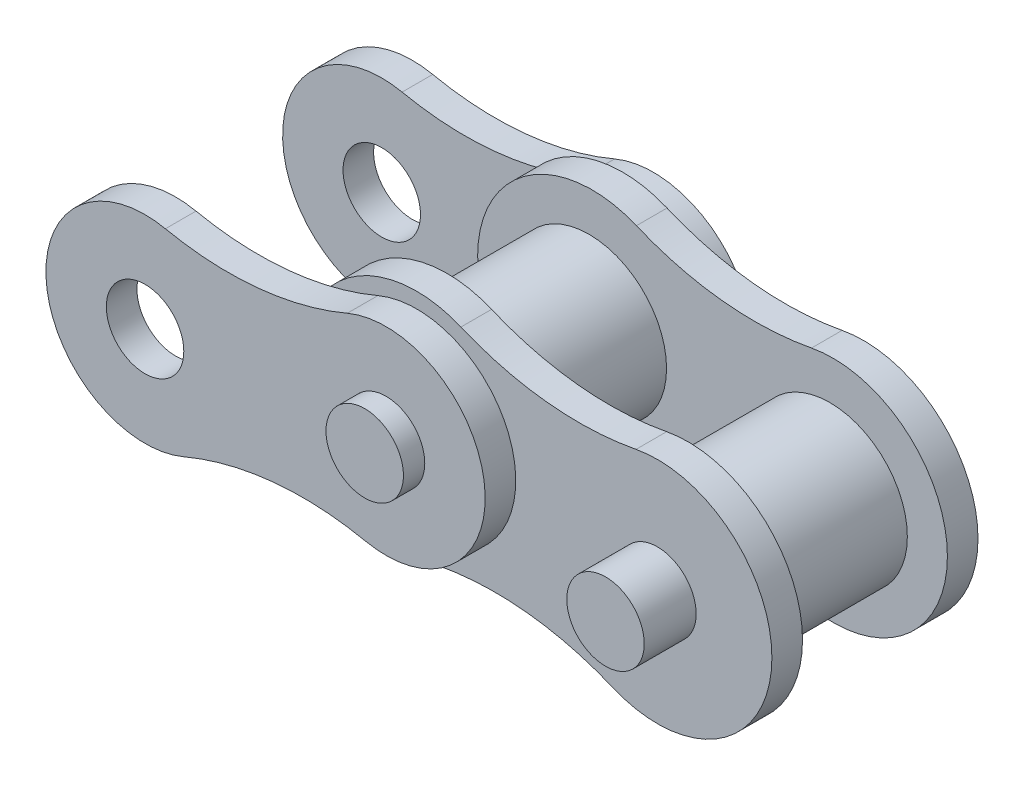
SolidWorks part; units mm, degrees
ref_plane "Front Plane" through (0, 0, 0) normal (0, 0, 1) x (1, 0, 0)
ref_plane "Top Plane" through (0, 0, 0) normal (0, 1, 0) x (1, 0, 0)
ref_plane "Right Plane" through (0, 0, 0) normal (1, 0, 0) x (0, 0, -1)
sketch "Sketch5" plane through (0, 0, 0) normal (0, 0, 1) x (1, 0, 0)
  line L0 (-11.651, 75.0374) -> (-172.0056, 50.1392) construction
  line L1 (-172.0056, -50.1392) -> (-11.651, -75.0374) construction
  arc A0 (-172.0056, 50.1392) -> (-172.0056, -50.1392) centre (-164.2205, 0) ccw construction
  arc A1 (-11.651, -75.0374) -> (-11.651, 75.0374) centre (0, 0) ccw construction
  spline S0 degree 3 poles (-11.5673, -75.0503) (37.9253, -82.6785) (75.9365, -50.077) (75.9365, 0) (75.9365, 50.077) (37.9253, 82.6785) (-11.5673, 75.0503) (-11.5766, 75.0489) (-11.5952, 75.046) (-11.6231, 75.0417) (-11.6417, 75.0388) (-11.651, 75.0374) (-11.66, 75.036) (-11.678, 75.0332) (-11.7051, 75.029) (-11.7231, 75.0262) (-11.7321, 75.0248) (-65.1307, 66.7336) (-118.5294, 58.4424) (-171.928, 50.1513) (-171.9366, 50.1499) (-171.9539, 50.1472) (-171.9797, 50.1432) (-171.997, 50.1405) (-172.0056, 50.1392) (-172.0132, 50.138) (-172.0285, 50.1356) (-172.0514, 50.1321) (-172.0667, 50.1297) (-172.0744, 50.1285) (-247.7088, 38.2785) (-247.7088, -38.2785) (-172.0744, -50.1285) (-172.0667, -50.1297) (-172.0514, -50.1321) (-172.0285, -50.1356) (-172.0132, -50.138) (-172.0056, -50.1392) (-171.997, -50.1405) (-171.9797, -50.1432) (-171.9539, -50.1472) (-171.9366, -50.1499) (-171.928, -50.1513) (-118.5294, -58.4424) (-65.1307, -66.7336) (-11.7321, -75.0248) (-11.7231, -75.0262) (-11.7051, -75.029) (-11.678, -75.0332) (-11.66, -75.036) (-11.651, -75.0374) (-11.6417, -75.0388) (-11.6231, -75.0417) (-11.5952, -75.046) (-11.5766, -75.0489) (-11.5673, -75.0503) (37.9253, -82.6785) (75.9365, -50.077) knots -0.000043 0 0 0 0.175818 0.175818 0.175818 0.351636 0.351636 0.351636 0.351679 0.351722 0.351765 0.351765 0.351765 0.351807 0.351849 0.35189 0.35189 0.35189 0.599139 0.599139 0.599139 0.599179 0.599219 0.599259 0.599259 0.599259 0.599294 0.59933 0.599365 0.599365 0.599365 0.752271 0.752271 0.752271 0.752306 0.752342 0.752377 0.752377 0.752377 0.752417 0.752457 0.752497 0.752497 0.752497 0.999746 0.999746 0.999746 0.999787 0.999829 0.999871 0.999871 0.999871 0.999914 0.999957 1 1 1 1.175818 1.175818 1.175818 weights 1 0.767351 0.767351 1 0.767351 0.767351 1 1 1 1 1 1 1 1 1 1 1 1 1 1 1 1 1 1 1 1 1 1 1 1 0.436524 0.436524 1 1 1 1 1 1 1 1 1 1 1 1 1 1 1 1 1 1 1 1 1 1 1 1 0.767351 0.767351 only from (-11.5673, -75.0503) to (-11.5673, -75.0503)
  dimension "D2" = 75.9365
  dimension "D1" = 50.74
  dimension "D3" = 164.2205
sketch "Sketch1" plane through (0, 0, 0) normal (0, 0, 1) x (1, 0, 0)
  line L1 (0, 75.9365) -> (15.788, 74.2771) construction
  arc A0 (2.9053, 82.8571) -> (1.4029, 68.5631) centre (0, 75.9365) ccw
  arc A1 (12.8828, 67.3565) -> (14.3851, 81.6505) centre (15.788, 74.2771) ccw
  arc A2 (14.3851, 81.6505) -> (2.9053, 82.8571) centre (10.6468, 101.2981) cw
  circle A3 centre (0, 75.9365) radius 2.54
  circle A4 centre (15.788, 74.2771) radius 2.54
  arc A5 (12.8828, 67.3565) -> (1.4029, 68.5631) centre (5.1412, 48.9156) ccw
  arc A6 (-11.651, -75.0374) -> (-11.651, 75.0374) centre (0, 0) ccw construction
  dimension "D1" = 15.0114
  dimension "D2" = 5.08
  dimension "D3" = 20
  dimension "D4" = 15.875
extrude "Boss-Extrude1" add sketch "Sketch1" along normal blind 2.0066 from offset 4.75
sketch "Sketch2" plane through (0, 0, 6.7566) normal (0, 0, 1) x (1, 0, 0)
  line L0 (0, 75.9365) -> (-15.7998, 74.3932) construction
  line L1 (0, 75.9365) -> (15.788, 74.2771) construction
  line L2 (-11.651, 75.0374) -> (-172.0056, 50.1392) construction
  arc A0 (-1.3348, 69.575) -> (-2.5406, 81.9194) centre (0, 75.9365) ccw
  arc A1 (-14.465, 80.7547) -> (-13.2592, 68.4103) centre (-15.7998, 74.3932) ccw
  arc A2 (-2.5406, 81.9194) -> (-14.465, 80.7547) centre (-10.3579, 100.3284) cw
  arc A3 (-13.2592, 68.4103) -> (-1.3348, 69.575) centre (-5.4419, 50.0013) cw
  circle A4 centre (0, 75.9365) radius 2.54
  circle A6 centre (-15.7998, 74.3932) radius 2.54
  circle A8 centre (0, 75.9365) radius 2.54 construction
  dimension "D1" = 13
  dimension "D3" = 20
extrude "Boss-Extrude2" add sketch "Sketch2" along normal blind 2.0066 separate body
mirror "Mirror1" about plane through (0, 0, 0) normal (0, 0, 1) of bodies 616 102 101 589 590 591 592 593 594 595 596 597 598 604 605 606 607 608 609 610 617 618 619 620 621 622 623 624 625 626 627 628 629 630 631 632 633 634 635 636
sketch "Sketch3" plane through (0, 0, 0) normal (0, 0, -1) x (-1, 0, 0)
  line L0 (0, 0) -> (0, -45.1396) construction
  circle A0 centre (0, 75.9365) radius 2.54 construction
  circle A1 centre (0, 75.9365) radius 2.54
  circle A3 centre (-15.788, 74.2771) radius 2.54 construction
  circle A5 centre (-15.788, 74.2771) radius 2.54
extrude "Boss-Extrude3" add sketch "Sketch3" along normal blind 10.16 and the other way blind 10.16 separate body
sketch "Sketch4" plane through (0, 0, 0) normal (0, 0, 1) x (1, 0, 0)
  line L0 (0, 0) -> (0, -48.4121) construction
  circle A0 centre (0, 75.9365) radius 5.08
  circle A1 centre (15.788, 74.2771) radius 5.08
  circle A2 centre (15.788, 74.2771) radius 2.54 construction
  dimension "D1" = 10.16
extrude "Boss-Extrude4" add sketch "Sketch4" along normal offset from surface 0.2 and the other way offset from surface 0.2 separate body up to face at (2.54, 75.9365, 4.75) other way up to face at (2.54, 75.9365, -4.75)
ref_axis "Axis1" through (-164.2205, 0, 0) along (0, 0, 1)
ref_axis "Axis2" through (0, 0, 0) along (0, 0, 1)
